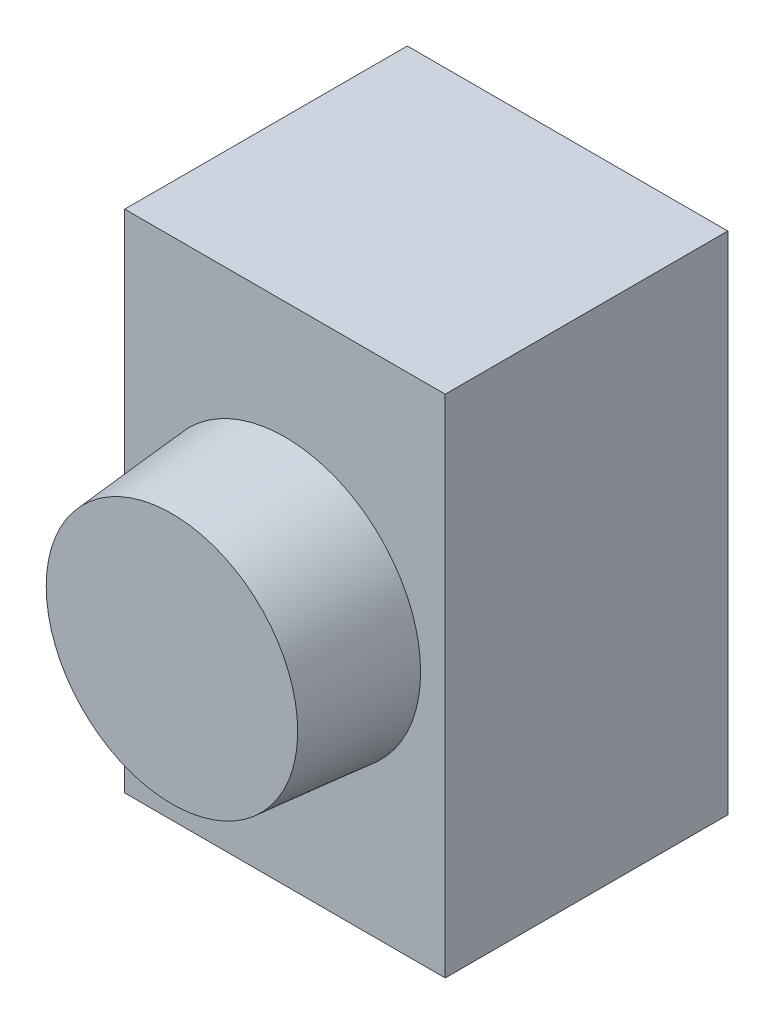
SolidWorks part; units mm, degrees
ref_plane "Front" through (0, 0, 0) normal (0, 0, 1) x (1, 0, 0)
ref_plane "Top" through (0, 0, 0) normal (0, 1, 0) x (1, 0, 0)
ref_plane "Right" through (0, 0, 0) normal (1, 0, 0) x (0, 0, -1)
sketch "Sketch1" plane through (0, 0, 0) normal (0, 0, 1) x (1, 0, 0)
  circle A0 centre (0, 0) radius 12
  dimension "D1" = 24
extrude "Boss-Extrude1" add sketch "Sketch1" along normal blind 10 draft 5
sketch "Sketch2" plane through (0, 0, 0) normal (0, 0, 1) x (1, 0, 0)
  line L1 (-14.1773, -22.3668) -> (14.1773, -22.3668)
  line L2 (-14.1773, -22.3668) -> (-14.1773, 22.3668)
  line L3 (-14.1773, 22.3668) -> (14.1773, 22.3668)
  line L4 (14.1773, -22.3668) -> (14.1773, 22.3668)
  line L5 (-14.1773, -22.3668) -> (14.1773, 22.3668) construction
  line L6 (-14.1773, 22.3668) -> (14.1773, -22.3668) construction
  point P0 (0, 0)
extrude "Boss-Extrude2" add sketch "Sketch2" against normal blind 25
sketch "Panel Cut Guide" plane through (0, 0, 0) normal (0, 0, 1) x (1, 0, 0)
  circle A0 centre (0, 0) radius 10
  dimension "D1" = 20
